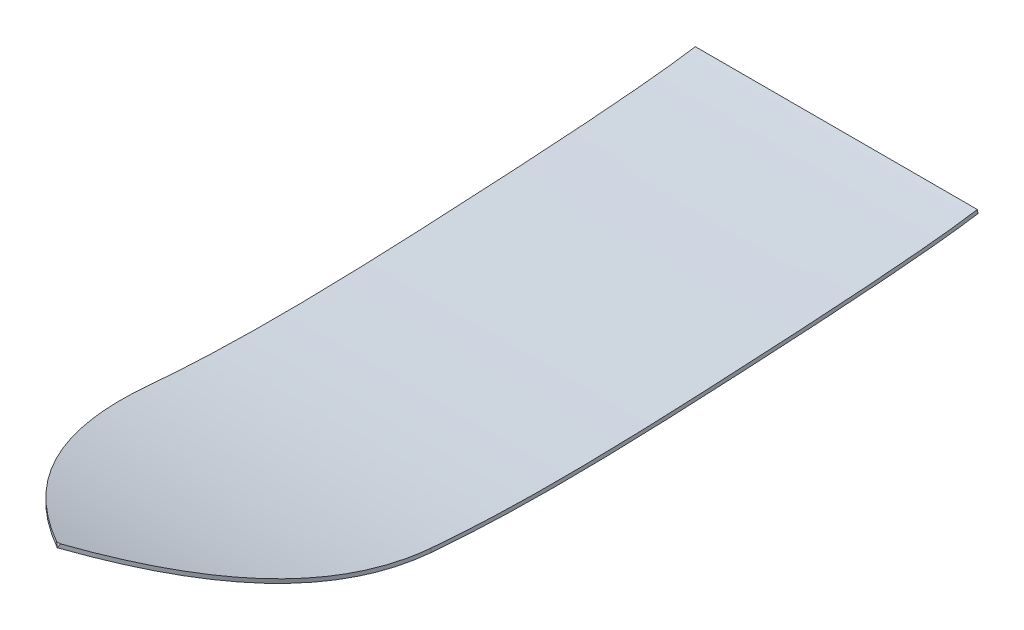
SolidWorks part; units mm, degrees
ref_plane "Front Plane" through (0, 0, 0) normal (0, 0, 1) x (1, 0, 0)
ref_plane "Top Plane" through (0, 0, 0) normal (0, 1, 0) x (1, 0, 0)
ref_plane "Right Plane" through (0, 0, 0) normal (1, 0, 0) x (0, 0, -1)
sketch "Sketch1" plane through (0, 0, 0) normal (1, 0, 0) x (0, 0, -1)
  line L24 (-2548.0474, 132.9276) -> (-2556.6069, 109.4385)
  line L25 (2415.7728, -57.2042) -> (2419.7915, -81.8791)
  spline S0 degree 3 poles (-2548.0474, 132.9276) (-2519.1858, 122.4104) (-2456.6488, 100.23) (-2360.3186, 68.0664) (-2258.6821, 36.3762) (-2122.1025, -3.2324) (-1983.1857, -39.0694) (-1840.1283, -71.4264) (-1730.1906, -94.0031) (-1635.8053, -111.4389) (-1558.2092, -124.5713) (-1479.0391, -137.1599) (-1376.7866, -151.8764) (-1268.9016, -165.2184) (-1178.1973, -175.0368) (-1119.2808, -180.8133) (-1077.0668, -184.6275) (-1028.2569, -188.8516) (-940.846, -195.7647) (-802.93, -204.4612) (-635.2835, -211.7905) (-487.0895, -215.54) (-363.6255, -217.0574) (-268.684, -217.4501) (-171.5475, -217.1017) (-72.4112, -216.0276) (28.4871, -214.2546) (130.8684, -211.8213) (234.4253, -208.7772) (338.8228, -205.1817) (443.7271, -201.1007) (548.7865, -196.6071) (653.7015, -191.7722) (758.1223, -186.6745) (861.8811, -181.3751) (964.4547, -175.9653) (1068.0764, -170.3416) (1276.1531, -158.6567) (1518.8865, -143.7259) (1978.3365, -110.4878) (2260.0013, -82.5742) (2415.7728, -57.2042) knots 0.004503 0.004503 0.004503 0.004503 0.03125 0.0625 0.09375 0.125 0.1875 0.21875 0.25 0.28125 0.296875 0.3125 0.34375 0.375 0.390625 0.40625 0.414062 0.417969 0.4375 0.46875 0.5 0.53125 0.546875 0.5625 0.578125 0.59375 0.609375 0.625 0.640625 0.65625 0.671875 0.6875 0.703125 0.71875 0.734375 0.75 0.765625 0.78125 0.84375 0.875 1 1 1 1
  spline S1 degree 1 poles (-2556.6069, 109.4385) (2419.7915, -81.8791) knots 0 0 1 1 construction
  spline S2 degree 3 poles (-2556.6069, 109.4385) (-2548.1846, 106.3695) (-2531.3122, 100.2688) (-2497.6074, 88.2719) (-2455.4663, 73.6268) (-2404.862, 56.6038) (-2337.2805, 34.6174) (-2252.4966, 8.429) (-2149.9186, -21.0349) (-2046.1254, -48.6314) (-1905.5161, -83.0286) (-1760.722, -113.9758) (-1609.2125, -141.6363) (-1491.334, -160.7549) (-1388.6518, -175.3316) (-1303.065, -186.1695) (-1236.9152, -193.8767) (-1168.4839, -201.16) (-1097.4359, -208.0004) (-1024.2226, -214.3083) (-923.5305, -221.9758) (-791.7257, -230.0822) (-623.6112, -237.1951) (-445.4434, -241.4824) (-257.608, -242.815) (-61.161, -241.1985) (142.1336, -236.8121) (315.2753, -231.15) (454.692, -225.6704) (559.3664, -221.1589) (663.8482, -216.3167) (767.8216, -211.2192) (871.0568, -205.9312) (973.2136, -200.532) (1076.4824, -194.9152) (1180.1073, -189.0822) (1283.717, -183.0275) (1421.217, -174.6531) (1556.8413, -165.8171) (1688.7648, -156.5003) (1785.3996, -149.2675) (1879.2692, -141.7846) (1969.9173, -134.0466) (2056.8886, -126.0486) (2139.7298, -117.785) (2204.9464, -110.6722) (2254.6055, -104.8426) (2290.5376, -100.3996) (2325.1023, -95.8846) (2352.7219, -92.061) (2374.0793, -88.9647) (2389.7243, -86.623) (2402.4365, -84.6568) (2412.4279, -83.0714) (2417.3297, -82.2801) (2419.7915, -81.8791) knots 0.004503 0.004503 0.004503 0.004503 0.012281 0.020058 0.035612 0.051167 0.066722 0.097831 0.12894 0.16005 0.191159 0.253377 0.284487 0.315596 0.346705 0.36226 0.377815 0.393369 0.408924 0.424478 0.440033 0.471142 0.502252 0.533361 0.56447 0.595579 0.626689 0.657798 0.673353 0.688907 0.704462 0.720017 0.735571 0.751126 0.76668 0.782235 0.79779 0.813344 0.844454 0.860008 0.875563 0.891118 0.906672 0.922227 0.937781 0.953336 0.961113 0.968891 0.976668 0.984445 0.988334 0.992223 0.996111 0.998056 1 1 1 1
  dimension "D1" = 25
extrude "Boss-Extrude1" add sketch "Sketch1" along normal blind 1524 and the other way blind 1524
sketch "Sketch3" plane through (0, 0, 0) normal (0, 1, 0) x (1, 0, 0)
  line L0 (-900, 2444.7524) -> (900, 2444.7524)
  line L1 (-900, 2444.7524) -> (-900, -1072.7812)
  line L2 (900, 2444.7524) -> (900, -1072.7812)
  line L3 (0, 2955.5244) -> (0, -2061.9995) construction
  line L4 (-2934.2017, 5372.0277) -> (2797.2556, 5372.0277)
  line L5 (-2934.2017, 5372.0277) -> (-2934.2017, -2631.2782)
  line L6 (-2934.2017, -2631.2782) -> (2797.2556, -2631.2782)
  line L7 (2797.2556, 5372.0277) -> (2797.2556, -2631.2782)
  line L8 (-94.9374, 0) -> (0, 0) construction
  line L11 (-1524, 1954.9582) -> (1524, 1954.9582) construction
  spline S0 degree 2 poles (-900, -1072.7812) (-900, -1947.4198) (0, -2556.6069) knots 0 0 0 1 1 1
  spline S1 degree 2 poles (900, -1072.7812) (900, -1947.4198) (0, -2556.6069) knots 0 0 0 1 1 1
  dimension "D1" = 1800
extrude "Cut-Extrude1" cut sketch "Sketch3" against normal through all both and the other way through all
